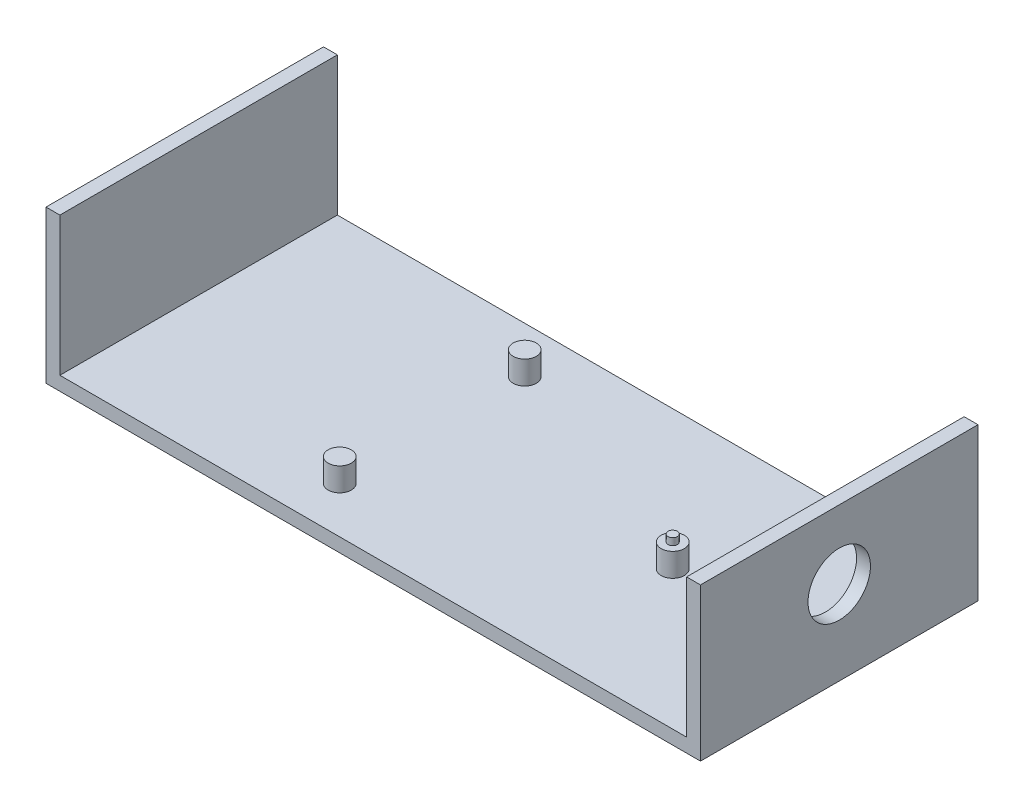
SolidWorks part; units mm, degrees
ref_plane "Front Plane" through (0, 0, 0) normal (0, 0, 1) x (1, 0, 0)
ref_plane "Top Plane" through (0, 0, 0) normal (0, 1, 0) x (1, 0, 0)
ref_plane "Right Plane" through (0, 0, 0) normal (1, 0, 0) x (0, 0, -1)
ref_plane "Bottom-side component clearance plane" through (0, -5.05, 0) normal (0, -1, 0) x (-1, 0, 0)
sketch "Sketch2" plane through (0, -5.05, 0) normal (0, -1, 0) x (-1, 0, 0)
  line L0 (-0.5074, 0) -> (-106.9926, 0) construction
  line L1 (0, 0.5074) -> (0, 49.4926) construction
  line L2 (-107.5, 0.5074) -> (-107.5, 11.1565) construction
  line L3 (-0.5074, 50) -> (-106.9926, 50) construction
  line L4 (30, 0) -> (-107.5, 0) construction
  line L5 (0, 0) -> (0, 50) construction
  line L6 (-107.5, 0) -> (-107.5, 50)
  line L7 (30, 50) -> (-107.5, 50) construction
  line L8 (30, 50) -> (30, 0)
  line L9 (30, -5) -> (-107.5, -5)
  line L10 (-107.5, -5) -> (-107.5, 0)
  line L11 (30, -5) -> (30, 0)
  line L12 (30, 50) -> (30, 55)
  line L13 (30, 55) -> (-107.5, 55)
  line L14 (-107.5, 55) -> (-107.5, 50)
  dimension "D1" = 30
  dimension "D2" = 5
  dimension "D3" = 5
extrude "Base" add sketch "Sketch2" along normal blind 3
sketch "Sketch3" plane through (0, -5.05, 0) normal (0, 1, 0) x (1, 0, 0)
  circle A0 centre (20.5, 5) radius 1.1 construction
  circle A1 centre (20.5, 45) radius 1.1 construction
  circle A2 centre (72.5, 25) radius 1.1 construction
  circle A3 centre (20.5, 5) radius 1.1 construction
  circle A4 centre (20.5, 45) radius 1.1 construction
  circle A5 centre (72.5, 25) radius 1.1 construction
  circle A6 centre (72.5, 25) radius 2.5
  circle A7 centre (20.5, 45) radius 2.5
  circle A8 centre (20.5, 5) radius 2.5
  dimension "D1" = 5
extrude "PCB mounting bosses" add sketch "Sketch3" along normal up to surface (5.05 mm away)
sketch "Sketch8" plane through (0, 0, 0) normal (0, 1, 0) x (1, 0, 0)
  circle A0 centre (72.5, 25) radius 1
  dimension "D1" = 2
extrude "Centering peg" add sketch "Sketch8" along normal blind 1.5
ref_plane "Connector wall minimum distance" through (-30, 0, 0) normal (-1, 0, 0) x (0, 0, 1)
sketch "Sketch4" plane through (-30, 0, 0) normal (-1, 0, 0) x (0, 0, 1)
  line L1 (-55, -8.05) -> (5, -8.05)
  line L2 (-55, -8.05) -> (-55, 24.95)
  line L3 (-55, 24.95) -> (5, 24.95)
  line L4 (5, -8.05) -> (5, 24.95)
  line L6 (5, -5.05) -> (-55, -5.05) construction
  dimension "D1" = 30
extrude "HV-side wall" add sketch "Sketch4" along normal blind 3
ref_plane "CAN connector mating plane" through (105.5, 0, 0) normal (1, 0, 0) x (0, 0, -1)
sketch "Sketch5" plane through (105.5, 0, 0) normal (1, 0, 0) x (0, 0, -1)
  line L1 (-5, -8.05) -> (55, -8.05)
  line L2 (-5, -8.05) -> (-5, 24.95)
  line L3 (-5, 24.95) -> (55, 24.95)
  line L4 (55, -8.05) -> (55, 24.95)
  line L6 (55, -8.05) -> (-5, -8.05) construction
  line L8 (55, -8.05) -> (55, -5.05) construction
  line L9 (-5, -8.05) -> (-5, -5.05) construction
  line L10 (55, -5.05) -> (-5, -5.05) construction
  dimension "D1" = 30
extrude "CAN connector mating wall" add sketch "Sketch5" along normal blind 3
sketch "Sketch6" plane through (108.5, 0, 0) normal (1, 0, 0) x (0, 0, -1)
  circle A0 centre (25, 10.1) radius 4.25 construction
  circle A1 centre (25, 10.1) radius 4.25 construction
  circle A2 centre (25, 10.1) radius 6.75
  dimension "D1" = 13.5
extrude "M12 connector cutout" cut sketch "Sketch6" against normal up to next
sketch "Sketch7" plane through (105.5, 0, 0) normal (-1, 0, 0) x (0, 0, 1)
  line L0 (-50, 1.6) -> (-37.7, 1.6)
  line L1 (-12.3, 1.6) -> (0, 1.6)
  line L2 (-12.3, 1.6) -> (0, 1.6) construction
  line L3 (-50, 1.6) -> (-37.7, 1.6) construction
  line L4 (-50, 0) -> (-37.7, 0)
  line L5 (-12.3, 0) -> (0, 0)
  line L6 (-12.3, 0) -> (0, 0)
  line L7 (-50, 0) -> (-37.7, 0)
  line L8 (0, 1.6) -> (0, 0) construction
  line L9 (0, 0) -> (0.5, 0)
  line L10 (0.5, 0) -> (0.5, 2)
  line L11 (0.5, 2) -> (-14.5, 2)
  line L12 (-14.5, 2) -> (-14.5, 0)
  line L13 (-14.5, 0) -> (-12.3, 0)
  line L14 (-25, 24.95) -> (-25, -5.05) construction
  line L15 (-55, 24.95) -> (5, 24.95) construction
  line L16 (5, -5.05) -> (-55, -5.05) construction
  line L17 (-50, 1.6) -> (-50, 0) construction
  line L18 (-37.7, 1.6) -> (-50, 1.6) construction
  line L19 (-35.5, 0) -> (-37.7, 0)
  line L20 (-35.5, 2) -> (-35.5, 0)
  line L21 (-50.5, 2) -> (-35.5, 2)
  line L22 (-50.5, 0) -> (-50.5, 2)
  line L23 (-50, 0) -> (-50.5, 0)
  line L24 (-37.7, 0) -> (-50, 0)
  dimension "D1" = 0.5
  dimension "D2" = 2
  dimension "D3" = 15
extrude "PCB tab slots" cut sketch "Sketch7" against normal blind 2 contours L23 L7 L19 L20 L21 L22 | L11 L12 L13 L6 L9 L10 region at (105.5, 1, -43)
equation "\"D3@Sketch2\"=\"D2@Sketch2\""
equation "\"Vertical wall height\"=30"
equation "\"D1@Sketch4\"=\"Vertical wall height\""
equation "\"D1@Sketch5\"=\"Vertical wall height\""
